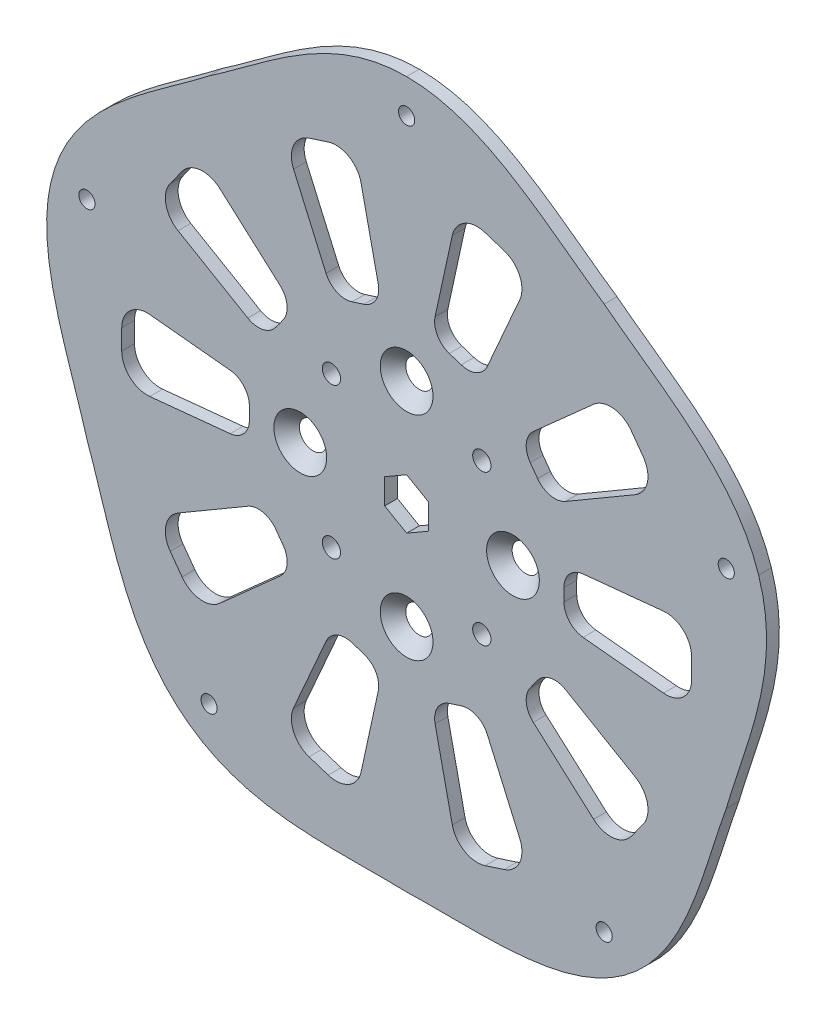
SolidWorks part; units mm, degrees
material "ABS"
ref_plane "Płaszczyzna przednia" through (0, 0, 0) normal (0, 0, 1) x (1, 0, 0)
ref_plane "Płaszczyzna górna" through (0, 0, 0) normal (0, 1, 0) x (1, 0, 0)
ref_plane "Płaszczyzna prawa" through (0, 0, 0) normal (1, 0, 0) x (0, 0, -1)
sketch "Szkic1" plane through (0, 0, 0) normal (0, 0, 1) x (1, 0, 0)
  line L0 (0, 0) -> (51.1373, 70.3845) construction
  line L1 (0, 0) -> (0, 87) construction
  line L2 (10.0308, 35.6449) -> (12.8365, 34.7333)
  line L3 (18.4501, 64.4532) -> (22.9582, 62.9884)
  line L4 (6.6904, 41.4644) -> (10.7335, 60.0239)
  line L5 (18.9595, 37.478) -> (26.5976, 54.8694)
  line L14 (30.082, -29.397) -> (44.2618, -42.0356)
  line L15 (55.8943, -37.2483) -> (53.1082, -41.0832)
  line L16 (37.6647, -18.9603) -> (54.0664, -28.5407)
  line L17 (31.0978, -20.3388) -> (29.3637, -22.7255)
  line L42 (-12.7931, 34.5999) -> (-9.9874, 35.5115) [skipped]
  line L43 (29.11, 23.0748) -> (30.844, 20.6881) [skipped]
  line L44 (-18.9162, 37.3446) -> (-26.5543, 54.7359) [skipped]
  line L45 (29.8282, 29.7463) -> (44.0081, 42.3848) [skipped]
  line L46 (-22.9149, 62.855) -> (-18.4067, 64.3198) [skipped]
  line L47 (52.8544, 41.4325) -> (55.6406, 37.5976) [skipped]
  line L48 (-6.6471, 41.331) -> (-10.6901, 59.8905) [skipped]
  line L49 (37.4109, 19.3096) -> (53.8127, 28.8899) [skipped]
  line L50 (-30.6438, 20.3388) -> (-28.9098, 22.7255) [skipped]
  line L51 (-37.2107, 18.9603) -> (-53.6125, 28.5407) [skipped]
  line L52 (-55.4404, 37.2483) -> (-52.6542, 41.0832) [skipped]
  line L53 (-29.628, 29.397) -> (-43.8079, 42.0356) [skipped]
  line L54 (-36.7029, -1.6909) -> (-36.7029, 1.2592) [skipped]
  line L55 (-41.2054, -6.6661) -> (-60.1059, -8.5562) [skipped]
  line L56 (-66.7029, -2.5859) -> (-66.7029, 2.1542) [skipped]
  line L57 (-41.2054, 6.2344) -> (-60.1059, 8.1244) [skipped]
  line L58 (-28.656, -23.0748) -> (-30.3901, -20.6881) [skipped]
  line L59 (-29.3743, -29.7463) -> (-43.5541, -42.3848) [skipped]
  line L60 (-52.4004, -41.4325) -> (-55.1866, -37.5976) [skipped]
  line L61 (-36.957, -19.3096) -> (-53.3587, -28.8899) [skipped]
  line L62 (-9.5768, -35.6449) -> (-12.3826, -34.7333) [skipped]
  line L63 (-6.2365, -41.4644) -> (-10.2795, -60.0239) [skipped]
  line L64 (-17.9961, -64.4532) -> (-22.5043, -62.9884) [skipped]
  line L65 (-18.5056, -37.478) -> (-26.1437, -54.8694) [skipped]
  line L66 (13.2471, -34.5999) -> (10.4414, -35.5115) [skipped]
  line L67 (19.3701, -37.3446) -> (27.0082, -54.7359) [skipped]
  line L68 (23.3688, -62.855) -> (18.8607, -64.3198) [skipped]
  line L69 (7.101, -41.331) -> (11.144, -59.8905) [skipped]
  line L70 (37.1568, 1.6909) -> (37.1568, -1.2592) [skipped]
  line L71 (41.6593, 6.6661) -> (60.5598, 8.5562) [skipped]
  line L72 (67.1568, 2.5859) -> (67.1568, -2.1542) [skipped]
  line L73 (41.6593, -6.2344) -> (60.5598, -8.1244) [skipped]
  line L74 (0, 0) -> (32.9395, 101.3773) construction
  line L75 (29.0524, 22.9527) -> (30.7864, 20.566)
  line L76 (29.7706, 29.6242) -> (43.9505, 42.2627)
  line L77 (52.7968, 41.3103) -> (55.583, 37.4754)
  line L78 (37.3533, 19.1874) -> (53.7551, 28.7678)
  line L79 (36.9808, 1.5038) -> (36.9808, -1.4463)
  line L80 (41.4833, 6.479) -> (60.3838, 8.369)
  line L81 (66.9808, 2.3988) -> (66.9808, -2.3413)
  line L82 (41.4833, -6.4215) -> (60.3838, -8.3116)
  line L83 (30.7878, -20.5089) -> (29.0537, -22.8956)
  line L84 (37.3547, -19.1304) -> (53.7565, -28.7108)
  line L85 (55.5844, -37.4184) -> (52.7982, -41.2533)
  line L86 (29.772, -29.5671) -> (43.9518, -42.2056)
  line L87 (12.8387, -34.6774) -> (10.033, -35.589)
  line L88 (18.9617, -37.4221) -> (26.5999, -54.8135)
  line L89 (22.9604, -62.9325) -> (18.4523, -64.3973)
  line L90 (6.6926, -41.4086) -> (10.7357, -59.9681)
  line L91 (-10.0104, -35.5898) -> (-12.8161, -34.6781)
  line L92 (-6.67, -41.4093) -> (-10.7131, -59.9688)
  line L93 (-18.4297, -64.398) -> (-22.9378, -62.9333)
  line L94 (-18.9391, -37.4228) -> (-26.5773, -54.8142)
  line L95 (-29.032, -22.8975) -> (-30.766, -20.5108)
  line L96 (-29.7502, -29.569) -> (-43.9301, -42.2075)
  line L97 (-52.7764, -41.2552) -> (-55.5626, -37.4203)
  line L98 (-37.3329, -19.1323) -> (-53.7347, -28.7127)
  line L99 (-36.9604, -1.4487) -> (-36.9604, 1.5015)
  line L100 (-41.4629, -6.4239) -> (-60.3634, -8.3139)
  line L101 (-66.9604, -2.3437) -> (-66.9604, 2.3965)
  line L102 (-41.4629, 6.4766) -> (-60.3634, 8.3667)
  line L103 (-30.7674, 20.5641) -> (-29.0333, 22.9508)
  line L104 (-37.3343, 19.1855) -> (-53.7361, 28.7659)
  line L105 (-55.564, 37.4735) -> (-52.7778, 41.3084)
  line L106 (-29.7516, 29.6223) -> (-43.9315, 42.2608)
  line L107 (-12.8183, 34.7325) -> (-10.0126, 35.6442)
  line L108 (-18.9414, 37.4772) -> (-26.5795, 54.8686)
  line L109 (-22.9401, 62.9877) -> (-18.4319, 64.4525)
  line L110 (-6.6723, 41.4637) -> (-10.7153, 60.0232)
  circle A0 centre (0, 0) radius 79 construction
  circle A2 centre (0, 0) radius 25 construction
  circle A3 centre (0, 0) radius 3.3
  circle A4 centre (0, 25) radius 3.2
  circle A5 centre (0, 79) radius 1.9
  circle A6 centre (25, 0) radius 3.2
  circle A7 centre (0, -25) radius 3.2
  circle A8 centre (-25, 0) radius 3.2
  circle A9 centre (75.1335, 24.4123) radius 1.9
  circle A10 centre (46.435, -63.9123) radius 1.9
  circle A11 centre (-46.435, -63.9123) radius 1.9
  circle A12 centre (-75.1335, 24.4123) radius 1.9
  circle A13 centre (0, 0) radius 87 construction
  arc A14 (26.5976, 54.8694) -> (22.9582, 62.9884) centre (21.1041, 57.2821) ccw
  arc A15 (18.4501, 64.4532) -> (10.7335, 60.0239) centre (16.596, 58.7468) ccw
  arc A16 (18.9595, 37.478) -> (12.8365, 34.7333) centre (14.3816, 39.4886) cw
  arc A17 (6.6904, 41.4644) -> (10.0308, 35.6449) centre (11.5758, 40.4002) ccw
  arc A54 (-18.9162, 37.3446) -> (-12.7931, 34.5999) centre (-14.3382, 39.3551) ccw [skipped]
  arc A55 (29.8282, 29.7463) -> (29.11, 23.0748) centre (33.155, 26.0137) ccw [skipped]
  arc A56 (-22.9149, 62.855) -> (-26.5543, 54.7359) centre (-21.0608, 57.1486) ccw [skipped]
  arc A57 (52.8544, 41.4325) -> (44.0081, 42.3848) centre (48.0003, 37.9057) ccw [skipped]
  arc A58 (-10.6901, 59.8905) -> (-18.4067, 64.3198) centre (-16.5526, 58.6134) ccw [skipped]
  arc A59 (53.8127, 28.8899) -> (55.6406, 37.5976) centre (50.7865, 34.0709) ccw [skipped]
  arc A60 (-6.6471, 41.331) -> (-9.9874, 35.5115) centre (-11.5325, 40.2668) cw [skipped]
  arc A61 (37.4109, 19.3096) -> (30.844, 20.6881) centre (34.8891, 23.627) cw [skipped]
  arc A62 (-37.2107, 18.9603) -> (-30.6438, 20.3388) centre (-34.6889, 23.2778) ccw [skipped]
  arc A63 (-55.4404, 37.2483) -> (-53.6125, 28.5407) centre (-50.5863, 33.7216) ccw [skipped]
  arc A64 (-43.8079, 42.0356) -> (-52.6542, 41.0832) centre (-47.8001, 37.5565) ccw [skipped]
  arc A65 (-29.628, 29.397) -> (-28.9098, 22.7255) centre (-32.9549, 25.6645) cw [skipped]
  arc A66 (-41.2054, -6.6661) -> (-36.7029, -1.6909) centre (-41.7029, -1.6909) ccw [skipped]
  arc A67 (-66.7029, -2.5859) -> (-60.1059, -8.5562) centre (-60.7029, -2.5859) ccw [skipped]
  arc A68 (-60.1059, 8.1244) -> (-66.7029, 2.1542) centre (-60.7029, 2.1542) ccw [skipped]
  arc A69 (-41.2054, 6.2344) -> (-36.7029, 1.2592) centre (-41.7029, 1.2592) cw [skipped]
  arc A70 (-29.3743, -29.7463) -> (-28.656, -23.0748) centre (-32.7011, -26.0137) ccw [skipped]
  arc A71 (-52.4004, -41.4325) -> (-43.5541, -42.3848) centre (-47.5463, -37.9057) ccw [skipped]
  arc A72 (-53.3587, -28.8899) -> (-55.1866, -37.5976) centre (-50.3325, -34.0709) ccw [skipped]
  arc A73 (-36.957, -19.3096) -> (-30.3901, -20.6881) centre (-34.4351, -23.627) cw [skipped]
  arc A74 (-6.2365, -41.4644) -> (-9.5768, -35.6449) centre (-11.1219, -40.4002) ccw [skipped]
  arc A75 (-17.9961, -64.4532) -> (-10.2795, -60.0239) centre (-16.142, -58.7468) ccw [skipped]
  arc A76 (-26.1437, -54.8694) -> (-22.5043, -62.9884) centre (-20.6502, -57.2821) ccw [skipped]
  arc A77 (-18.5056, -37.478) -> (-12.3826, -34.7333) centre (-13.9276, -39.4886) cw [skipped]
  arc A78 (19.3701, -37.3446) -> (13.2471, -34.5999) centre (14.7922, -39.3551) ccw [skipped]
  arc A79 (23.3688, -62.855) -> (27.0082, -54.7359) centre (21.5147, -57.1486) ccw [skipped]
  arc A80 (11.144, -59.8905) -> (18.8607, -64.3198) centre (17.0066, -58.6134) ccw [skipped]
  arc A81 (7.101, -41.331) -> (10.4414, -35.5115) centre (11.9864, -40.2668) cw [skipped]
  arc A82 (37.6647, -18.9603) -> (31.0978, -20.3388) centre (35.1428, -23.2778) ccw [skipped]
  arc A83 (55.8943, -37.2483) -> (54.0664, -28.5407) centre (51.0402, -33.7216) ccw [skipped]
  arc A84 (44.2618, -42.0356) -> (53.1082, -41.0832) centre (48.2541, -37.5565) ccw [skipped]
  arc A85 (30.082, -29.397) -> (29.3637, -22.7255) centre (33.4088, -25.6645) cw [skipped]
  arc A86 (41.6593, 6.6661) -> (37.1568, 1.6909) centre (42.1568, 1.6909) ccw [skipped]
  arc A87 (67.1568, 2.5859) -> (60.5598, 8.5562) centre (61.1568, 2.5859) ccw [skipped]
  arc A88 (60.5598, -8.1244) -> (67.1568, -2.1542) centre (61.1568, -2.1542) ccw [skipped]
  arc A89 (41.6593, -6.2344) -> (37.1568, -1.2592) centre (42.1568, -1.2592) cw [skipped]
  circle A90 centre (0, 0) radius 37 construction
  arc A91 (37.3533, 19.1874) -> (30.7864, 20.566) centre (34.8315, 23.5049) cw
  arc A92 (29.7706, 29.6242) -> (29.0524, 22.9527) centre (33.0974, 25.8916) ccw
  arc A93 (52.7968, 41.3103) -> (43.9505, 42.2627) centre (47.9427, 37.7836) ccw
  arc A94 (53.7551, 28.7678) -> (55.583, 37.4754) centre (50.7289, 33.9487) ccw
  arc A95 (41.4833, -6.4215) -> (36.9808, -1.4463) centre (41.9808, -1.4463) cw
  arc A96 (41.4833, 6.479) -> (36.9808, 1.5038) centre (41.9808, 1.5038) ccw
  arc A97 (66.9808, 2.3988) -> (60.3838, 8.369) centre (60.9808, 2.3988) ccw
  arc A98 (60.3838, -8.3116) -> (66.9808, -2.3413) centre (60.9808, -2.3413) ccw
  arc A99 (29.772, -29.5671) -> (29.0537, -22.8956) centre (33.0988, -25.8346) cw
  arc A100 (37.3547, -19.1304) -> (30.7878, -20.5089) centre (34.8329, -23.4479) ccw
  arc A101 (55.5844, -37.4184) -> (53.7565, -28.7108) centre (50.7302, -33.8917) ccw
  arc A102 (43.9518, -42.2056) -> (52.7982, -41.2533) centre (47.9441, -37.7266) ccw
  arc A103 (6.6926, -41.4086) -> (10.033, -35.589) centre (11.5781, -40.3443) cw
  arc A104 (18.9617, -37.4221) -> (12.8387, -34.6774) centre (14.3838, -39.4327) ccw
  arc A105 (22.9604, -62.9325) -> (26.5999, -54.8135) centre (21.1063, -57.2262) ccw
  arc A106 (10.7357, -59.9681) -> (18.4523, -64.3973) centre (16.5982, -58.691) ccw
  arc A107 (-18.9391, -37.4228) -> (-12.8161, -34.6781) centre (-14.3612, -39.4334) cw
  arc A108 (-6.67, -41.4093) -> (-10.0104, -35.5898) centre (-11.5555, -40.3451) ccw
  arc A109 (-18.4297, -64.398) -> (-10.7131, -59.9688) centre (-16.5756, -58.6917) ccw
  arc A110 (-26.5773, -54.8142) -> (-22.9378, -62.9333) centre (-21.0837, -57.2269) ccw
  arc A111 (-37.3329, -19.1323) -> (-30.766, -20.5108) centre (-34.8111, -23.4497) cw
  arc A112 (-29.7502, -29.569) -> (-29.032, -22.8975) centre (-33.0771, -25.8364) ccw
  arc A113 (-52.7764, -41.2552) -> (-43.9301, -42.2075) centre (-47.9223, -37.7284) ccw
  arc A114 (-53.7347, -28.7127) -> (-55.5626, -37.4203) centre (-50.7085, -33.8936) ccw
  arc A115 (-41.4629, 6.4766) -> (-36.9604, 1.5015) centre (-41.9604, 1.5015) cw
  arc A116 (-41.4629, -6.4239) -> (-36.9604, -1.4487) centre (-41.9604, -1.4487) ccw
  arc A117 (-66.9604, -2.3437) -> (-60.3634, -8.3139) centre (-60.9604, -2.3437) ccw
  arc A118 (-60.3634, 8.3667) -> (-66.9604, 2.3965) centre (-60.9604, 2.3965) ccw
  arc A119 (-29.7516, 29.6223) -> (-29.0333, 22.9508) centre (-33.0784, 25.8897) cw
  arc A120 (-37.3343, 19.1855) -> (-30.7674, 20.5641) centre (-34.8125, 23.503) ccw
  arc A121 (-55.564, 37.4735) -> (-53.7361, 28.7659) centre (-50.7099, 33.9468) ccw
  arc A122 (-43.9315, 42.2608) -> (-52.7778, 41.3084) centre (-47.9237, 37.7817) ccw
  arc A123 (-6.6723, 41.4637) -> (-10.0126, 35.6442) centre (-11.5577, 40.3995) cw
  arc A124 (-18.9414, 37.4772) -> (-12.8183, 34.7325) centre (-14.3634, 39.4878) ccw
  arc A125 (-22.9401, 62.9877) -> (-26.5795, 54.8686) centre (-21.086, 57.2813) ccw
  arc A126 (-10.7153, 60.0232) -> (-18.4319, 64.4525) centre (-16.5778, 58.7461) ccw
  spline S0 degree 3 poles (0, 87) (18.2248, 86.9986) (32.2889, 73.5369) (46.435, 63.9123) knots 0 0 0 0 1 1 1 1
  spline S1 degree 3 poles (82.7419, 26.8845) (77.1088, 44.2169) (59.9599, 53.4327) (46.435, 63.9123) knots 0 0 0 0 1 1 1 1
  spline S2 degree 3 poles (82.7419, 26.8845) (88.3724, 9.5512) (79.9156, -7.9844) (75.1335, -24.4123) knots 0 0 0 0 1 1 1 1
  spline S3 degree 3 poles (51.1373, -70.3845) (65.8807, -59.6711) (69.3462, -40.5137) (75.1335, -24.4123) knots 0 0 0 0 1 1 1 1
  spline S4 degree 3 poles (51.1373, -70.3845) (36.3923, -81.0957) (17.1016, -78.4715) (0, -79) knots 0 0 0 0 1 1 1 1
  spline S5 degree 3 poles (-51.1373, -70.3845) (-36.3923, -81.0957) (-17.1016, -78.4715) (0, -79) knots 0 0 0 0 1 1 1 1
  spline S6 degree 3 poles (-51.1373, -70.3845) (-65.8807, -59.6711) (-69.3462, -40.5137) (-75.1335, -24.4123) knots 0 0 0 0 1 1 1 1
  spline S7 degree 3 poles (-82.7419, 26.8845) (-88.3724, 9.5512) (-79.9156, -7.9844) (-75.1335, -24.4123) knots 0 0 0 0 1 1 1 1
  spline S8 degree 3 poles (-82.7419, 26.8845) (-77.1088, 44.2169) (-59.9599, 53.4327) (-46.435, 63.9123) knots 0 0 0 0 1 1 1 1
  spline S9 degree 3 poles (0, 87) (-18.2248, 86.9986) (-32.2889, 73.5369) (-46.435, 63.9123) knots 0 0 0 0 1 1 1 1
  point P18 (0, 0)
  point P27 (0, 0)
  point P43 (11.4336, 35.1891)
  point P64 (0, 0)
  point P65 (20.7041, 63.7208)
  point P67 (29.2636, 60.9396)
  point P70 (12.1446, 66.5019)
  point P73 (17.14, 33.335)
  point P76 (5.7273, 37.0432)
  point P188 (0.227, 0)
  point P369 (0.0102, 0.0276)
  dimension "D1" = 158
  dimension "D2" = 6.6
  dimension "D3" = 50
  dimension "D4" = 3.8
  dimension "D5" = 6.4
  dimension "D8" = 174
  dimension "D13" = 74
  dimension "D14" = 6
  dimension "D15" = 5
  dimension "D9" = 36
  dimension "D10" = 12
  dimension "D11" = 18
  dimension "D12" = 30
  dimension "D17" = 18
  dimension "D6" = 4
  dimension "D7" = 5
  dimension "D16" = 10
  dimension "D18" = 10
extrude "Dodanie-wyciągnięcie1" add sketch "Szkic1" along normal blind 3
sketch "Sketch1" plane through (0, 0, 0) normal (0, 0, -1) x (-1, 0, 0)
  line L0 (0, 0) -> (-16.4631, 16.4631) construction
  line L1 (0, 0) -> (14.4362, 0) construction
  circle A0 centre (0, 0) radius 25 construction
  circle A1 centre (-17.6777, 17.6777) radius 2.15
  circle A2 centre (17.6777, 17.6777) radius 2.15
  circle A3 centre (17.6777, -17.6777) radius 2.15
  circle A4 centre (-17.6777, -17.6777) radius 2.15
  point P17 (0, 0)
  dimension "D1" = 135
  dimension "D2" = 4.3
  dimension "D3" = 4
extrude "Cut-Extrude1" cut sketch "Sketch1" against normal blind 7
chamfer "Chamfer1" distance 3 angle 45 4 edges at (28.2, 0, 3) (-21.8, 0, 3) (3.2, 25, 3) (3.2, -25, 3)
sketch "Sketch2" plane through (0, 0, 3) normal (0, 0, 1) x (1, 0, 0)
  line L1 (-5.15, 2.9734) -> (-5.15, -2.9734)
  line L2 (-5.15, -2.9734) -> (0, -5.9467)
  line L3 (0, -5.9467) -> (5.15, -2.9734)
  line L4 (5.15, -2.9734) -> (5.15, 2.9734)
  line L5 (5.15, 2.9734) -> (0, 5.9467)
  line L6 (0, 5.9467) -> (-5.15, 2.9734)
  circle A0 centre (0, 0) radius 5.15 construction
  dimension "D1" = 10.3
extrude "Cut-Extrude2" cut sketch "Sketch2" against normal blind 5.5
